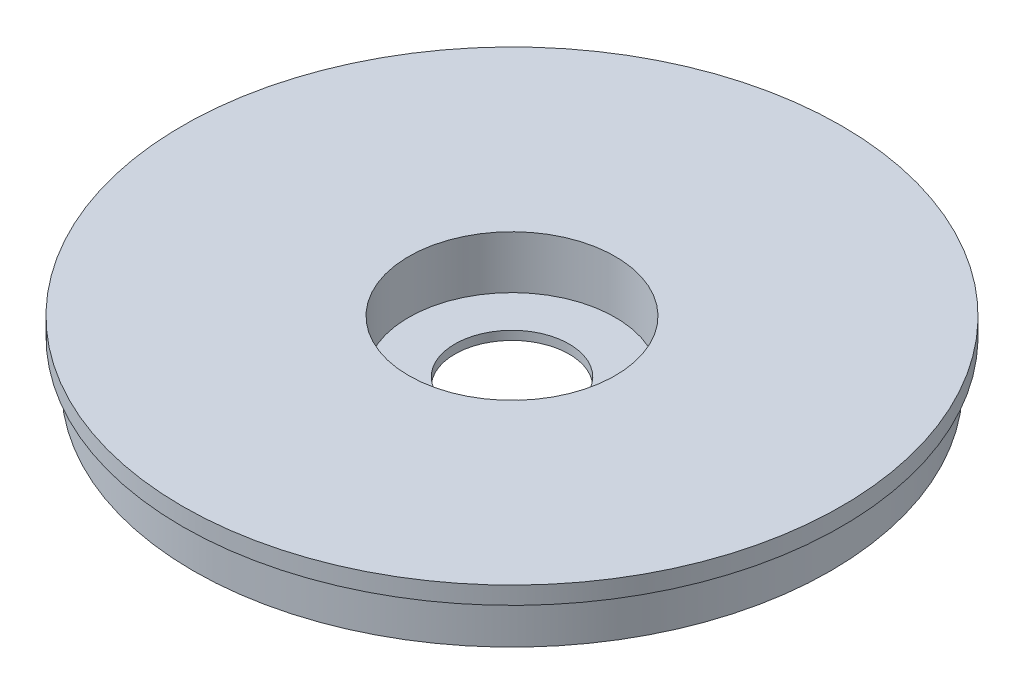
SolidWorks part; units mm, degrees
ref_plane "Płaszczyzna przednia" through (0, 0, 0) normal (0, 0, 1) x (1, 0, 0)
ref_plane "Płaszczyzna górna" through (0, 0, 0) normal (0, 1, 0) x (1, 0, 0)
ref_plane "Płaszczyzna prawa" through (0, 0, 0) normal (1, 0, 0) x (0, 0, -1)
sketch "Szkic4" plane through (0, 0, 0) normal (0, 1, 0) x (1, 0, 0)
  circle A0 centre (0, 0) radius 75
extrude "Dodanie-wyciągnięcie2" add sketch "Szkic4" along normal blind 14
sketch "Szkic5" plane through (0, 14, 0) normal (0, 1, 0) x (1, 0, 0)
  circle A0 centre (0, 0) radius 23.5
extrude "Wytnij-wyciągnięcie3" cut sketch "Szkic5" against normal blind 12
sketch "Szkic6" plane through (0, 2, 0) normal (0, 1, 0) x (1, 0, 0)
  circle A0 centre (0, 0) radius 13
  dimension "D1" = 26
extrude "Wytnij-wyciągnięcie4" cut sketch "Szkic6" against normal blind 12
sketch "Szkic7" plane through (0, 0, 0) normal (0, -1, 0) x (1, 0, 0)
  circle A0 centre (0, 0) radius 75
  circle A1 centre (0, 0) radius 72.5
  circle A2 centre (0, 0) radius 75 construction
  dimension "D1" = 2.5
extrude "Wytnij-wyciągnięcie5" cut sketch "Szkic7" against normal blind 10
sketch "Szkic9" plane through (0, 0, 0) normal (0, -1, 0) x (-1, 0, 0)
  circle A0 centre (21.6549, 28.26) radius 2.5
  circle A1 centre (12.9418, 33.1674) radius 2.5
extrude "Wytnij-wyciągnięcie6" cut sketch "Szkic9" against normal blind 5
ref_plane "Płaszczyzna1" through (71.9446, 0, -8.9569) normal (0.9923, 0, -0.1235) x (-0.1235, 0, -0.9923)
